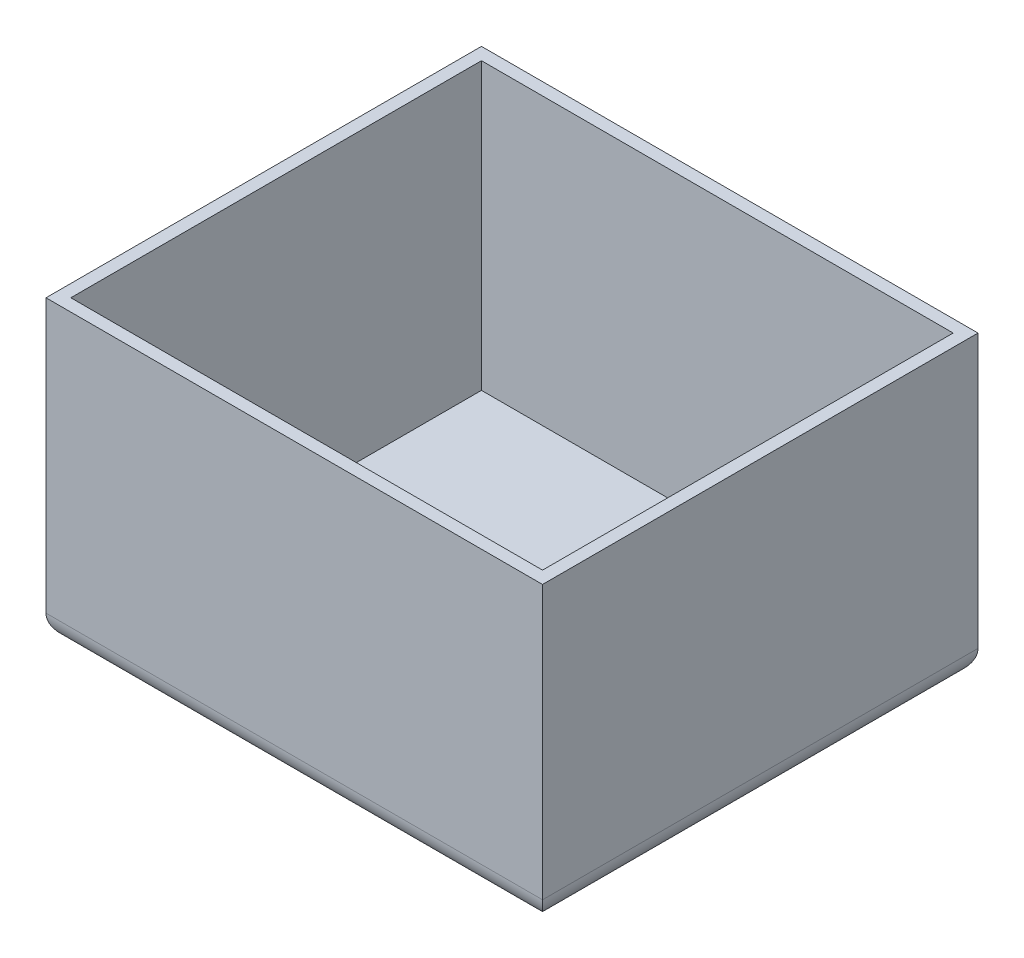
SolidWorks part; units mm, degrees
ref_plane "Front Plane" through (0, 0, 0) normal (0, 0, 1) x (1, 0, 0)
ref_plane "Top Plane" through (0, 0, 0) normal (0, 1, 0) x (1, 0, 0)
ref_plane "Right Plane" through (0, 0, 0) normal (1, 0, 0) x (0, 0, -1)
sketch "Sketch2" plane through (0, 0, 0) normal (0, 0, 1) x (1, 0, 0)
  line L1 (0, 0) -> (200, 0)
  line L2 (0, 0) -> (0, 120)
  line L3 (0, 120) -> (200, 120)
  line L4 (200, 0) -> (200, 120)
  dimension "D1" = 120
  dimension "D2" = 200
extrude "Boss-Extrude1" add sketch "Sketch2" along normal blind 175.4
shell "Shell1" thickness 5 removed face at (100, 120, 87.7)
sketch "Sketch3" plane through (0, 0, 0) normal (0, -1, 0) x (1, 0, 0)
  line L7 (66.6641, 82.4026) -> (132.5422, 82.4026)
  line L8 (66.6641, 82.4026) -> (66.6641, 93.5146)
  line L9 (66.6641, 93.5146) -> (132.5422, 93.5146)
  line L10 (132.5422, 82.4026) -> (132.5422, 93.5146)
extrude "Boss-Extrude2" add sketch "Sketch3" along normal blind 25 contours L8 L7 L10 L9
sketch "Sketch4" plane through (0, 0, 93.5146) normal (0, 0, 1) x (1, 0, 0)
  line L1 (70.8258, -3.7156) -> (128.5828, -3.7156)
  line L2 (70.8258, -3.7156) -> (70.8258, -20.0768)
  line L3 (70.8258, -20.0768) -> (128.5828, -20.0768)
  line L4 (128.5828, -3.7156) -> (128.5828, -20.0768)
extrude "Cut-Extrude1" cut sketch "Sketch4" against normal blind 13
fillet "Fillet1" radius 10 8 edges at (0, 0, 87.7) (100, 0, 175.4) (200, 0, 87.7) (100, 0, 0) (99.6031, 0, 82.4026) (132.5422, 0, 87.9586) (99.6031, 0, 93.5146) (66.6641, 0, 87.9586)
